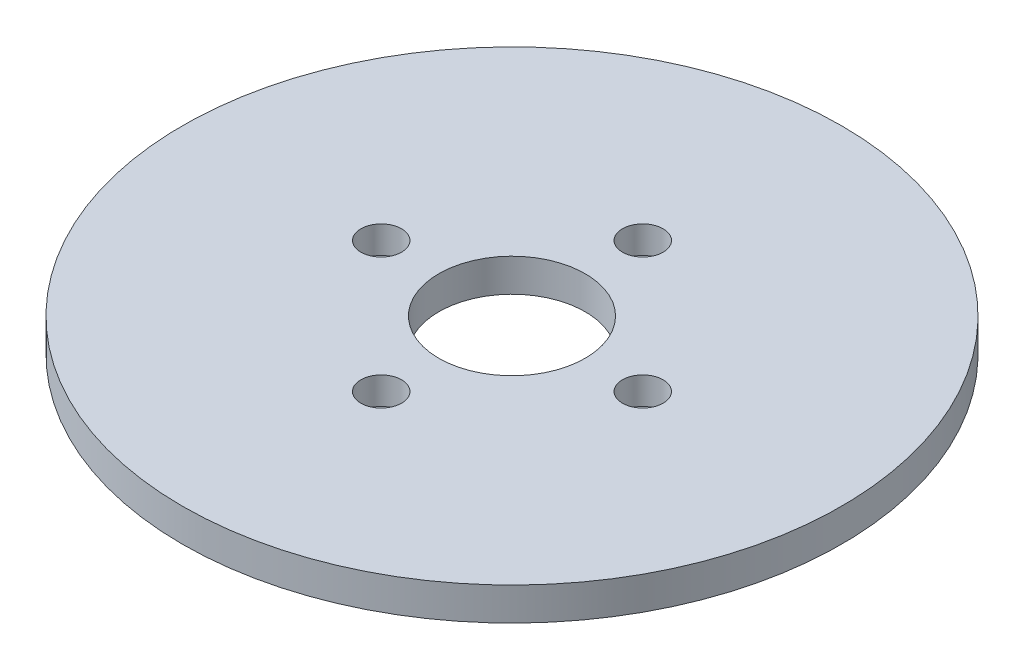
SolidWorks part; units mm, degrees
ref_plane "Front Plane" through (0, 0, 0) normal (0, 0, 1) x (1, 0, 0)
ref_plane "Top Plane" through (0, 0, 0) normal (0, 1, 0) x (1, 0, 0)
ref_plane "Right Plane" through (0, 0, 0) normal (1, 0, 0) x (0, 0, -1)
sketch "Sketch1" plane through (0, 0, 0) normal (0, 1, 0) x (1, 0, 0)
  circle A0 centre (0, 0) radius 90
  dimension "FLANGE_OD" = 180
extrude "Boss-Extrude1" add sketch "Sketch1" along normal blind 9
sketch "Sketch2" plane through (0, 0, 0) normal (0, 1, 0) x (1, 0, 0)
  circle A0 centre (0, 0) radius 20
  dimension "BORE_D" = 40
extrude "Cut-Extrude1" cut sketch "Sketch2" along normal through all
sketch "Sketch3" plane through (0, 9, 0) normal (0, 1, 0) x (1, 0, 0)
  circle A0 centre (0, 0) radius 35.7145 construction
  circle A1 centre (-35.7145, 0) radius 5.5512
  dimension "BOLT_D" = 11.1025
  dimension "BOLT_PCD" = 71.4291
extrude "Cut-Extrude2" cut sketch "Sketch3" against normal blind 7.4677
pattern_circular "CirPattern1" count 4 over 360 about axis through (0, 0, 0) along (0, 1, 0) of "Cut-Extrude2"
